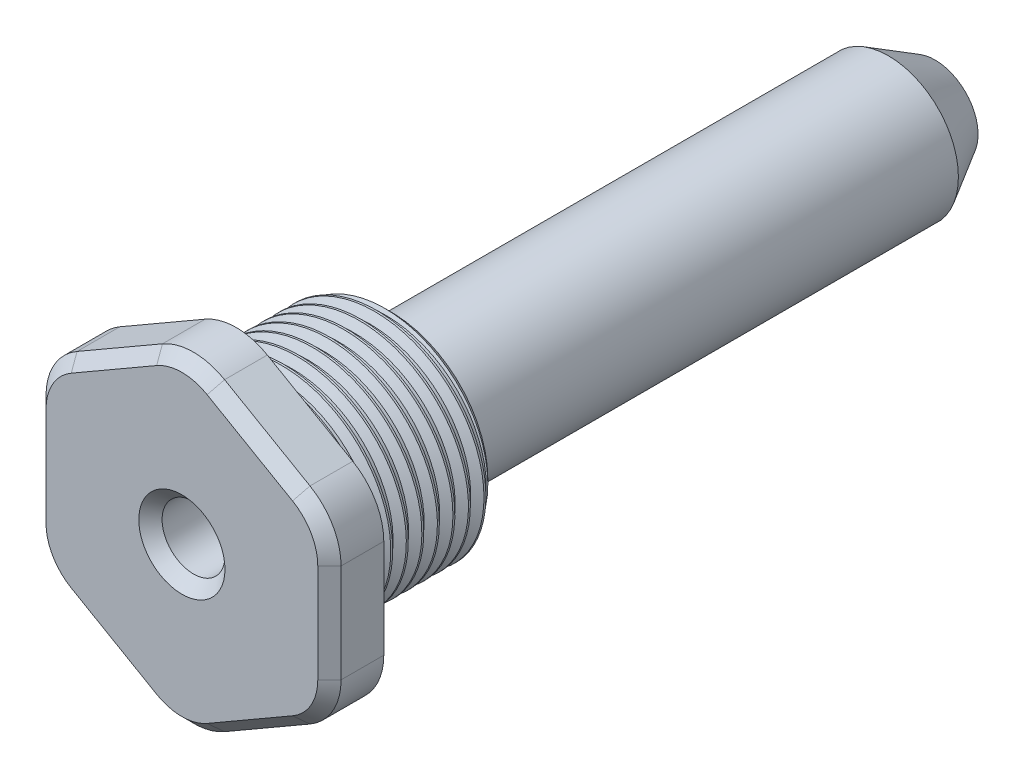
SolidWorks part; units mm, degrees
ref_plane "Front Plane" through (0, 0, 0) normal (0, 0, 1) x (1, 0, 0)
ref_plane "Top Plane" through (0, 0, 0) normal (0, 1, 0) x (1, 0, 0)
ref_plane "Right Plane" through (0, 0, 0) normal (1, 0, 0) x (0, 0, -1)
sketch "Sketch1" plane through (0, 0, 0) normal (0, 0, 1) x (1, 0, 0)
  circle A0 centre (0, 0) radius 6.95
  dimension "D1" = 13.9
extrude "Boss-Extrude1" add sketch "Sketch1" along normal blind 10
chamfer "Chamfer1" distance 0.75 angle 45 1 edges at (6.95, 0, 0)
sketch "Sketch2" plane through (0, 0, 10) normal (0, 0, 1) x (1, 0, 0)
  circle A0 centre (0, 0) radius 6.95 construction
  circle A1 centre (0, 0) radius 6.95
curve "Helix/Spiral1" pitch 1 height 11 radius 6.95 centre (0, 0, 10) axis (0, 0, -1) start towards (1, 0, 0)
sketch "Sketch3" plane through (0, 0, 0) normal (0, 1, 0) x (1, 0, 0)
  line L0 (6.1922, -10.4375) -> (7.1083, -10.4375) construction
  line L1 (7.0583, -9.9375) -> (6.1922, -9.4375) construction
  line L2 (6.1922, -9.4375) -> (6.1922, -11.4375) construction
  line L3 (6.1922, -10.4375) -> (7.0583, -9.9375) construction
  line L4 (7.0583, -10.9375) -> (6.1922, -11.4375) construction
  line L5 (6.1922, -10.4375) -> (7.0583, -10.9375) construction
  line L6 (6.95, -10.875) -> (6.95, -11) construction
  line L7 (6.4087, -10.3125) -> (6.4087, -10.5625)
  line L8 (6.4087, -10.5625) -> (6.95, -10.875)
  line L9 (6.95, -10.875) -> (6.95, -10)
  line L10 (6.95, -10) -> (6.4087, -10.3125)
  circle A0 centre (6.4809, -9.9375) radius 0.2887 construction
  dimension "D1" = 1
  dimension "D2" = 0.125
  dimension "D3" = 0.25
sweep "Cut-Sweep1" cut profiles "Sketch3" path "Helix/Spiral1" align with end faces yes
sketch "Sketch4" plane through (0, 0, 10) normal (0, 0, 1) x (1, 0, 0)
  line L1 (0, 10.9697) -> (-9.5, 5.4848)
  line L2 (-9.5, 5.4848) -> (-9.5, -5.4848)
  line L3 (-9.5, -5.4848) -> (0, -10.9697)
  line L4 (0, -10.9697) -> (9.5, -5.4848)
  line L5 (9.5, -5.4848) -> (9.5, 5.4848)
  line L6 (9.5, 5.4848) -> (0, 10.9697)
  circle A0 centre (0, 0) radius 9.5 construction
  dimension "D1" = 19
  dimension "D2" = 21.9393
extrude "Boss-Extrude2" add sketch "Sketch4" along normal blind 3.5
fillet "Fillet1" radius 4 6 edges at (9.5, -5.4848, 11.75) (0, -10.9697, 11.75) (-9.5, -5.4848, 11.75) (-9.5, 5.4848, 11.75) (0, 10.9697, 11.75) (9.5, 5.4848, 11.75)
chamfer "Chamfer3" distance 0.75 angle 45 12 edges at (0, -10.3509, 13.5) (-4.75, -8.2272, 13.5) (-8.9641, -5.1754, 13.5) (-9.5, 0, 13.5) (-8.9641, 5.1754, 13.5) (-4.75, 8.2272, 13.5) (0, 10.3509, 13.5) (4.75, 8.2272, 13.5) (8.9641, 5.1754, 13.5) (9.5, 0, 13.5) (8.9641, -5.1754, 13.5) (4.75, -8.2272, 13.5)
sketch "Sketch5" plane through (0, 0, 0) normal (0, 0, -1) x (-1, 0, 0)
  circle A0 centre (0, 0) radius 4.5
  dimension "D1" = 9
extrude "Boss-Extrude3" add sketch "Sketch5" along normal blind 35
fillet "Fillet2" radius 0.5 1 edges at (4.5, 0, 0)
sketch "Sketch6" plane through (0, 0, 13.5) normal (0, 0, 1) x (1, 0, 0)
  circle A0 centre (0, 0) radius 2.025
  dimension "D1" = 4.05
extrude "Cut-Extrude1" cut sketch "Sketch6" against normal blind 30
chamfer "Chamfer4" distance 3.4 angle 30 1 edges at (2.025, 0, -16.5) first distance on face at (2.025, 0, -16.5)
chamfer "Chamfer5" distance 3 angle 30 1 edges at (-4.5, 0, -35) first distance on face at (4.5, 0, -0.5)
chamfer "Chamfer6" distance 0.75 angle 45 1 edges at (2.025, 0, 13.5)
equation "\"D2@Sketch3\"=1/8"
equation "\"D3@Sketch3\"=1/4"
